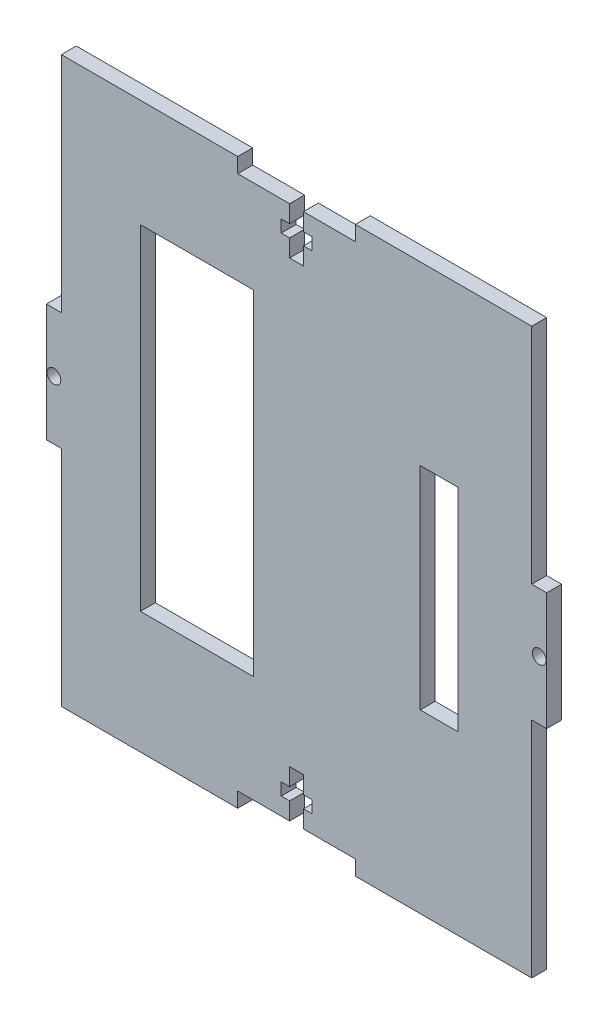
SolidWorks part; units mm, degrees
ref_plane "Front Plane" through (0, 0, 0) normal (0, 0, 1) x (1, 0, 0)
ref_plane "Top Plane" through (0, 0, 0) normal (0, 1, 0) x (1, 0, 0)
ref_plane "Right Plane" through (0, 0, 0) normal (1, 0, 0) x (0, 0, -1)
sketch "Sketch1" plane through (0, 0, 0) normal (0, 0, 1) x (1, 0, 0)
  line L0 (0, 60) -> (0, -60) construction
  line L1 (-50, 60) -> (50, 60)
  line L2 (-50, 60) -> (-50, -60)
  line L3 (-50, -60) -> (50, -60)
  line L4 (50, 60) -> (50, -60)
  line L5 (-50, 60) -> (50, -60) construction
  line L6 (-50, -60) -> (50, 60) construction
  line L7 (-50, 0) -> (50, 0) construction
  line L8 (-3.25, -50.525) -> (3.25, -50.525)
  line L9 (12.5, 60) -> (-12.5, 60)
  line L10 (12.5, 60) -> (12.5, 56.825)
  line L11 (12.5, 56.825) -> (-12.5, 56.825)
  line L12 (-12.5, 60) -> (-12.5, 56.825)
  line L13 (12.5, 60) -> (-12.5, 56.825) construction
  line L14 (12.5, 56.825) -> (-12.5, 60) construction
  line L15 (-1.47, 56.825) -> (1.47, 56.825)
  line L16 (-1.47, 56.825) -> (-1.47, 46.825)
  line L17 (-1.47, 46.825) -> (1.47, 46.825)
  line L18 (1.47, 56.825) -> (1.47, 46.825)
  line L19 (-1.47, 56.825) -> (1.47, 46.825) construction
  line L20 (-1.47, 46.825) -> (1.47, 56.825) construction
  line L21 (-3.25, 53.125) -> (3.25, 53.125)
  line L22 (-3.25, 53.125) -> (-3.25, 50.525)
  line L23 (-3.25, 50.525) -> (3.25, 50.525)
  line L24 (3.25, 53.125) -> (3.25, 50.525)
  line L25 (-3.25, 53.125) -> (3.25, 50.525) construction
  line L26 (-3.25, 50.525) -> (3.25, 53.125) construction
  line L27 (3.25, -53.125) -> (3.25, -50.525)
  line L28 (-3.25, -53.125) -> (3.25, -53.125)
  line L29 (-3.25, -53.125) -> (-3.25, -50.525)
  line L30 (-1.47, -46.825) -> (1.47, -46.825)
  line L31 (1.47, -56.825) -> (1.47, -46.825)
  line L32 (-1.47, -56.825) -> (1.47, -56.825)
  line L33 (-1.47, -56.825) -> (-1.47, -46.825)
  line L34 (12.5, -56.825) -> (-12.5, -56.825)
  line L35 (-12.5, -60) -> (-12.5, -56.825)
  line L36 (12.5, -60) -> (-12.5, -60)
  line L37 (12.5, -60) -> (12.5, -56.825)
  line L38 (53.175, -12.5) -> (50, -12.5)
  line L39 (-53.175, 12.5) -> (-50, 12.5)
  line L40 (-53.175, 12.5) -> (-53.175, -12.5)
  line L41 (-53.175, -12.5) -> (-50, -12.5)
  line L42 (-50, 12.5) -> (-50, -12.5)
  line L43 (-53.175, 12.5) -> (-50, -12.5) construction
  line L44 (-53.175, -12.5) -> (-50, 12.5) construction
  line L45 (50, 12.5) -> (50, -12.5)
  line L46 (53.175, 12.5) -> (50, 12.5)
  line L47 (53.175, 12.5) -> (53.175, -12.5)
  circle A0 centre (-51.5875, 0) radius 1.47
  circle A1 centre (51.5875, 0) radius 1.47
  point P0 (0, 0)
  point P10 (0, 58.4125)
  point P15 (0, 51.825)
  point P20 (0, 51.825)
  point P37 (-51.5875, 0)
  dimension "D11" = 2.94
  dimension "D1" = 120
  dimension "D2" = 100
  dimension "D3" = 3.175
  dimension "D4" = 10
  dimension "D5" = 2.94
  dimension "D6" = 25
  dimension "D7" = 6.5
  dimension "D8" = 2.6
  dimension "D9" = 6.3
  dimension "D10" = 3.175
extrude "Boss-Extrude1" add sketch "Sketch1" along normal mid plane 3.175 contours L21 L24 L23 L18 L17 L16 L22 L11 L12 L1 L2 L3 L4 L10 | L40 L39 L42 L41 | A0 | L38 L45 L46 L47 | A1 region at (0, 0, 0)
sketch "Sketch3" plane through (0, 0, -1.5875) normal (0, 0, -1) x (-1, 0, 0)
  line L6 (-30.3, 22.5) -> (-30.3, -22.5) construction
  line L7 (-26.3, 22.5) -> (-34.3, 22.5)
  line L8 (-26.3, 22.5) -> (-26.3, -22.5)
  line L9 (-26.3, -22.5) -> (-34.3, -22.5)
  line L10 (-34.3, 22.5) -> (-34.3, -22.5)
  line L11 (-28.7125, -25) -> (-28.7125, 25) construction
  line L12 (-31.8875, 25) -> (-31.8875, -25) construction
  line L13 (0, 0) -> (-5.1205, 0) construction
  dimension "D1" = 8
  dimension "D2" = 45
extrude "Cut-Extrude1" cut sketch "Sketch3" against normal through all
sketch "Sketch4" plane through (0, 0, -1.5875) normal (0, 0, -1) x (-1, 0, 0)
  line L0 (33.2, 36.2555) -> (33.2, -33.2445) construction
  line L1 (33.2, 37.1055) -> (9.2, 37.1055)
  line L2 (33.2, 37.1055) -> (33.2, -34.0945)
  line L3 (33.2, -34.0945) -> (9.2, -34.0945)
  line L4 (9.2, 37.1055) -> (9.2, -34.0945)
  line L5 (9.2, -33.2445) -> (9.2, 36.2555) construction
  line L6 (10.05, 37.1055) -> (16.7, 37.1055) construction
  line L7 (32.35, -34.0945) -> (10.05, -34.0945) construction
extrude "Cut-Extrude2" cut sketch "Sketch4" against normal through all
